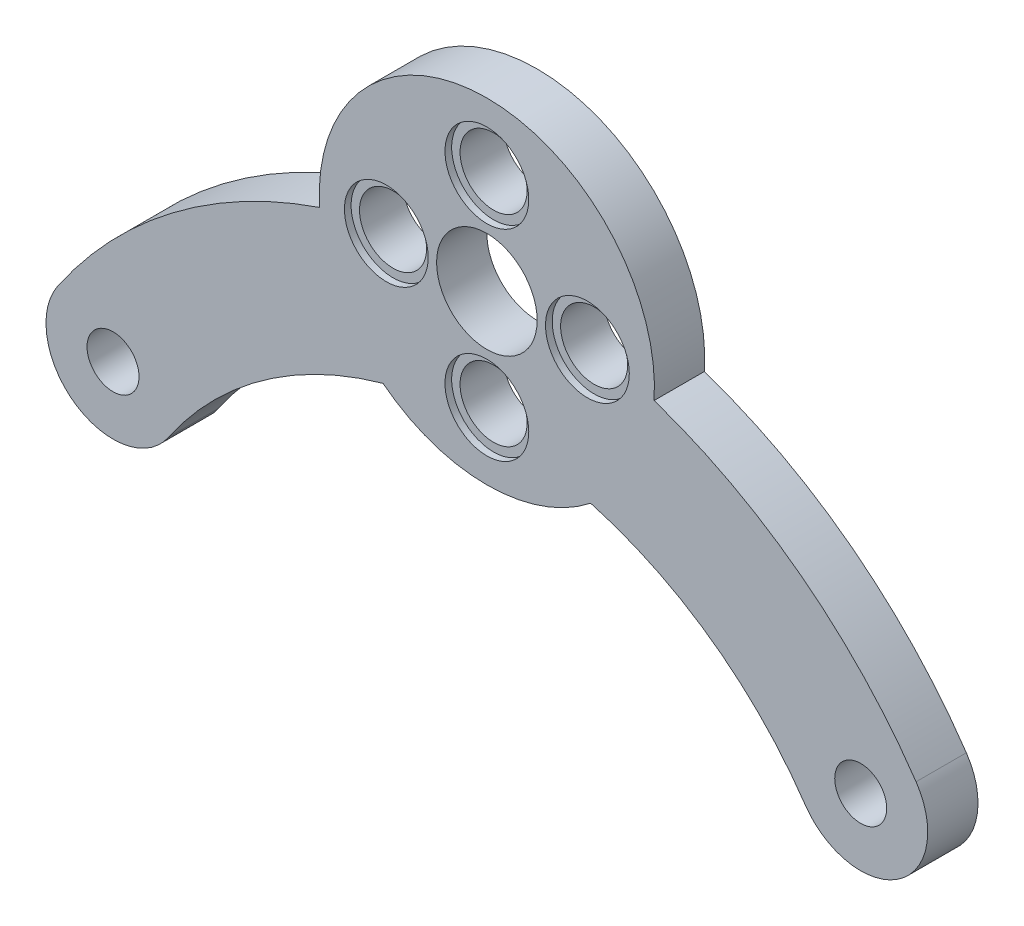
SolidWorks part; units mm, degrees
ref_plane "Front" through (0, 0, 0) normal (0, 0, 1) x (1, 0, 0)
ref_plane "Top" through (0, 0, 0) normal (0, 1, 0) x (1, 0, 0)
ref_plane "Right" through (0, 0, 0) normal (1, 0, 0) x (0, 0, -1)
sketch "Esquisse1" plane through (0, 0, 0) normal (0, 0, 1) x (1, 0, 0)
  line L0 (0, 0) -> (0, 30) construction
  line L1 (0, 30) -> (0, 40) construction
  line L2 (27.9166, 13.4783) -> (20.7123, 10)
  line L3 (20.7123, 10) -> (0, 0) construction
  line L4 (-27.9166, 13.4783) -> (-20.7123, 10)
  arc A0 (9.9789, 29.35) -> (-9.9789, 29.35) centre (0, 30) ccw
  arc A1 (-20.7123, 10) -> (20.7123, 10) centre (0, 0) cw
  arc A2 (9.9789, 29.35) -> (27.9166, 13.4783) centre (0, 0) cw
  arc A3 (-9.9789, 29.35) -> (-27.9166, 13.4783) centre (0, 0) ccw
  dimension "D2" = 23
  dimension "D1" = 10
  dimension "D3" = 30
  dimension "D4" = 8
  dimension "D5" = 10
extrude "Boss.-Extru.1" add sketch "Esquisse1" along normal blind 3
sketch "Esquisse3" plane through (0, 0, 3) normal (0, 0, 1) x (1, 0, 0)
  circle A0 centre (0, 30) radius 10
  arc A1 (9.9789, 29.35) -> (-9.9789, 29.35) centre (0, 30) ccw construction
extrude "Boss.-Extru.2" add sketch "Esquisse3" against normal up to vertex (3 mm away) up to point (27.9166, 13.4783, 0)
fillet "Congé1" radius 4 4 edges at (-27.9166, 13.4783, 1.5) (-20.7123, 10, 1.5) (20.7123, 10, 1.5) (27.9166, 13.4783, 1.5)
sketch "Esquisse2" plane through (0, 0, 3) normal (0, 0, 1) x (1, 0, 0)
  line L0 (0, 30) -> (6, 30) construction
  circle A0 centre (0, 30) radius 3
  circle A1 centre (6, 30) radius 2
  circle A2 centre (0, 24) radius 2
  circle A3 centre (-6, 30) radius 2
  circle A4 centre (0, 36) radius 2
  point P14 (0, 30)
  dimension "D1" = 6
  dimension "D2" = 4
  dimension "D3" = 6
  dimension "D4" = 4
extrude "Enlèv. mat.-Extru.1" cut sketch "Esquisse2" against normal through all both and the other way through all
sketch "Esquisse4" plane through (0, 0, 3) normal (0, 0, 1) x (1, 0, 0)
  circle A0 centre (22.307, 15.2117) radius 1.55
  circle A1 centre (-22.307, 15.2117) radius 1.55
  dimension "D1" = 3.1
extrude "Enlèv. mat.-Extru.2" cut sketch "Esquisse4" against normal through all both and the other way through all
sketch "Esquisse5" plane through (0, 0, 3) normal (0, 0, 1) x (1, 0, 0)
  circle A0 centre (0, 24) radius 2.5
  circle A1 centre (6, 30) radius 2.5
  circle A2 centre (0, 36) radius 2.5
  circle A3 centre (-6, 30) radius 2.5
  dimension "D1" = 5
extrude "Enlèv. mat.-Extru.3" cut sketch "Esquisse5" against normal blind 0.4
